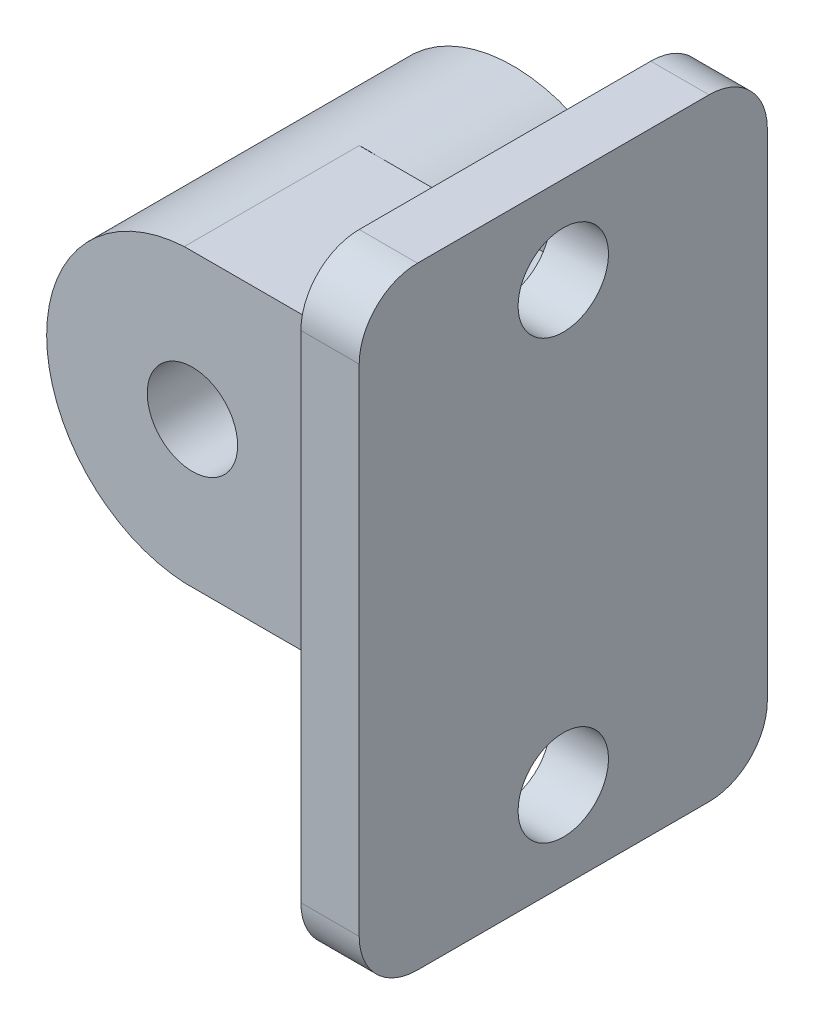
SolidWorks part; units mm, degrees
ref_plane "Plan de face" through (0, 0, 0) normal (0, 0, 1) x (1, 0, 0)
ref_plane "Plan de dessus" through (0, 0, 0) normal (0, 1, 0) x (1, 0, 0)
ref_plane "Plan de droite" through (0, 0, 0) normal (1, 0, 0) x (0, 0, -1)
sketch "Esquisse1" plane through (0, 0, 0) normal (0, 0, 1) x (1, 0, 0)
  line L0 (-0.2792, 4.9922) -> (7.7208, 4.9922)
  line L1 (14.9398, 0) -> (50014.9398, 0) construction
  line L2 (-0.2792, -4.9922) -> (7.7208, -4.9922)
  line L3 (7.7208, 4.9922) -> (7.7208, -4.9922)
  arc A1 (-0.2792, 4.9922) -> (-0.2792, -4.9922) centre (0, 0) ccw
  circle A3 centre (0, 0) radius 1.55
  dimension "D1" = 3.1
  dimension "D2" = 10
  dimension "D3" = 8
extrude "Boss.-Extru.1" add sketch "Esquisse1" along normal blind 3 and the other way blind 3
sketch "Sketch1" plane through (7.7208, 0, 0) normal (1, 0, 0) x (0, 0, -1)
  line L6 (-7, -10.5) -> (7, -10.5)
  line L7 (-7, -10.5) -> (-7, 10.5)
  line L8 (-7, 10.5) -> (7, 10.5)
  line L9 (7, -10.5) -> (7, 10.5)
  line L10 (-7, -10.5) -> (7, 10.5) construction
  line L11 (-7, 10.5) -> (7, -10.5) construction
  point P0 (0, 0)
  dimension "D1" = 21
  dimension "D2" = 14
extrude "Boss-Extrude1" add sketch "Sketch1" along normal blind 2
sketch "Sketch2" plane through (9.7208, 0, 0) normal (1, 0, 0) x (0, 0, -1)
  circle A0 centre (0, 0) radius 3.81
  circle A1 centre (0, 0) radius 4.81
  point P0 (0, 0)
  dimension "D1" = 7.62
  dimension "D2" = 1
extrude "Boss-Extrude2" [suppressed] add sketch "Sketch2" along normal blind 17.78
sketch "Sketch3" plane through (7.7208, 0, 0) normal (-1, 0, 0) x (0, 0, 1)
  line L0 (0, 0) -> (50000, 0) construction
  circle A0 centre (0, 7.5) radius 1.55
  circle A1 centre (0, -7.5) radius 1.55
  point P7 (0, 6.9959)
  point P8 (0, 7.8913)
  dimension "D1" = 3.1
  dimension "D2" = 7.5
extrude "Cut-Extrude1" cut sketch "Sketch3" against normal up to surface (2 mm away) up to face at (9.7208, 0, 0)
fillet "Fillet1" radius 2 4 edges at (8.7208, 10.5, 7) (8.7208, -10.5, 7) (8.7208, -10.5, -7) (8.7208, 10.5, -7)
sketch "Sketch4" plane through (0, 0, -3) normal (0, 0, 1) x (1, 0, 0)
  circle A0 centre (0, 0) radius 1.55
  circle A1 centre (0, 0) radius 5
  arc A2 (-0.2792, 4.9922) -> (-0.2792, -4.9922) centre (0, 0) ccw construction
extrude "Boss-Extrude3" add sketch "Sketch4" against normal blind 5
